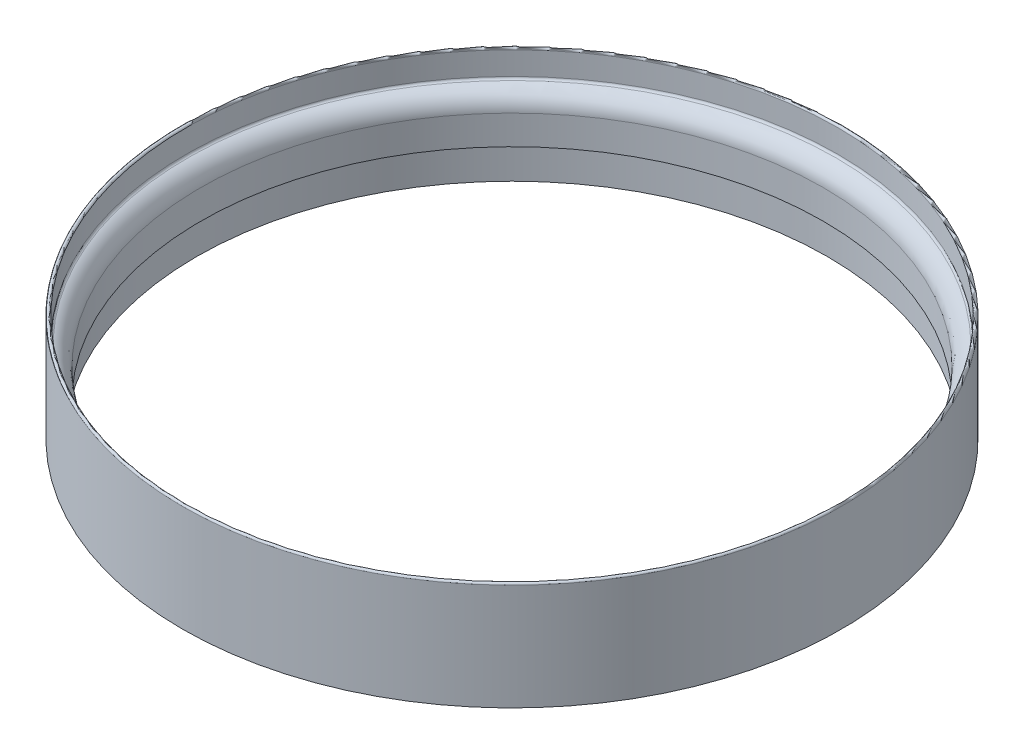
SolidWorks part; units mm, degrees
ref_plane "Front Plane" through (0, 0, 0) normal (0, 0, 1) x (1, 0, 0)
ref_plane "Top Plane" through (0, 0, 0) normal (0, 1, 0) x (1, 0, 0)
ref_plane "Right Plane" through (0, 0, 0) normal (1, 0, 0) x (0, 0, -1)
sketch "Sketch1" plane through (0, 0, 0) normal (1, 0, 0) x (0, 0, -1)
  line L0 (0, 0) -> (0, 21.8072) construction
  line L1 (-104.902, 0) -> (-100.457, 0)
  line L2 (-100.457, 0) -> (-100.457, 10.5)
  line L3 (-100.457, 10.5) -> (-99.06, 10.5)
  line L4 (-99.06, 10.5) -> (-99.06, 19.771)
  line L5 (-99.06, 19.771) -> (-103.8225, 19.771) construction
  line L6 (-103.8225, 19.771) -> (-103.8225, 34.376) construction
  line L7 (-103.8225, 34.376) -> (-104.902, 34.376)
  line L8 (-104.902, 34.376) -> (-104.902, 0)
  line L9 (-103.8225, 25.9194) -> (-103.8225, 34.376)
  arc A0 (-99.06, 19.771) -> (-103.8225, 25.9194) centre (-105.41, 19.771) ccw
  dimension "D8" = 6.35
  dimension "D1" = 10.5
  dimension "D2" = 9.271
  dimension "D3" = 14.605
  dimension "D4" = 200.914
  dimension "D5" = 198.12
  dimension "D6" = 103.8225
  dimension "D7" = 209.804
revolve "Revolve1" add sketch "Sketch1" angle 360 about L0
fillet "Fillet1" radius 0.7937 2 edges at (0, 10.5, -100.457) (0, 25.9194, -103.8225)
fillet "Fillet2" 2 edges at (0, 34.376, -104.902) (0, 34.376, -103.8225) type full round first side face at (0, 0, -104.902) second side face at (0, 26.5062, -103.8225) middle face at (0, 34.376, -104.902)
equation "\"bottom_bearing_thickness\"=0.413386"
equation "\"D1@Sketch1\"=\"bottom_bearing_thickness\""
equation "\"middle_thick\"=0.365"
equation "\"D2@Sketch1\"=\"middle_thick\""
equation "\"printer_limit\"=8.26"
equation "\"D7@Sketch1\"=\"printer_limit\""
